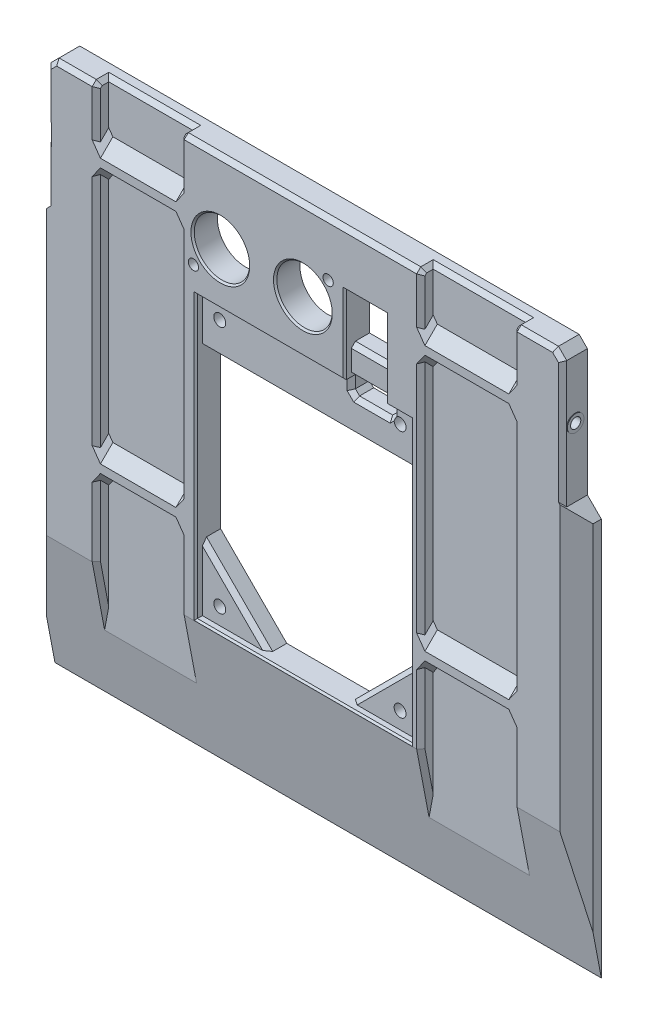
SolidWorks part; units mm, degrees
ref_plane "Front Plane" through (0, 0, 0) normal (0, 0, 1) x (1, 0, 0)
ref_plane "Top Plane" through (0, 0, 0) normal (0, 1, 0) x (1, 0, 0)
ref_plane "Right Plane" through (0, 0, 0) normal (1, 0, 0) x (0, 0, -1)
sketch "Sketch1" plane through (0, 0, 0) normal (0, 0, 1) x (1, 0, 0)
  line L1 (82.55, 82.55) -> (-82.55, 82.55)
  line L2 (82.55, 82.55) -> (82.55, -82.55)
  line L3 (82.55, -82.55) -> (-82.55, -82.55)
  line L4 (-82.55, 82.55) -> (-82.55, -82.55)
  line L5 (82.55, 82.55) -> (-82.55, -82.55) construction
  line L6 (82.55, -82.55) -> (-82.55, 82.55) construction
  point P0 (0, 0)
  dimension "D1" = 165.1
  dimension "D2" = 165.1
extrude "Boss-Extrude1" add sketch "Sketch1" along normal blind 7.5
sketch "Sketch2" plane through (0, 0, 7.5) normal (0, 0, 1) x (1, 0, 0)
  line L1 (-32.5, 42.5) -> (32.5, 42.5)
  line L2 (-32.5, 42.5) -> (-32.5, -42.5)
  line L3 (-32.5, -42.5) -> (32.5, -42.5)
  line L4 (32.5, 42.5) -> (32.5, -42.5)
  line L5 (-32.5, 42.5) -> (32.5, -42.5) construction
  line L6 (-32.5, -42.5) -> (32.5, 42.5) construction
  line L7 (12.5, 42.5) -> (25, 42.5)
  line L8 (12.5, 42.5) -> (12.5, 51.2227)
  line L9 (12.5, 51.2227) -> (25, 51.2227)
  line L10 (25, 42.5) -> (25, 51.2227)
  point P0 (0, 0)
  dimension "D1" = 65
  dimension "D2" = 85
  dimension "D3" = 12.5
  dimension "D4" = 7.5
extrude "Cut-Extrude1" cut sketch "Sketch2" against normal blind 2 contours L4 L1 L2 L3 | L1 L10 L9 L8
sketch "Sketch3" plane through (0, 0, 5.5) normal (0, 0, 1) x (1, 0, 0)
  line L1 (-27.25, -37.5) -> (27.25, -37.5) construction
  line L2 (-27.25, -37.5) -> (-27.25, 37.5) construction
  line L3 (-27.25, 37.5) -> (27.25, 37.5) construction
  line L4 (27.25, -37.5) -> (27.25, 37.5) construction
  line L5 (-27.25, -37.5) -> (27.25, 37.5) construction
  line L6 (-27.25, 37.5) -> (27.25, -37.5) construction
  circle A0 centre (-27.25, 37.5) radius 1.8
  circle A1 centre (27.25, 37.5) radius 1.8
  circle A3 centre (-27.25, -37.5) radius 1.8
  circle A4 centre (27.25, -37.5) radius 1.8
  point P0 (0, 0)
  point P7 (-27.25, 37.5)
  point P8 (27.25, 37.5)
  point P9 (-27.25, -37.5)
  point P10 (27.25, -37.5)
  dimension "D3" = 3.6
  dimension "D4" = 3.6
  dimension "D5" = 3.6
  dimension "D6" = 3.6
  dimension "D1" = 54.5
  dimension "D2" = 75
extrude "Cut-Extrude2" cut sketch "Sketch3" against normal through all
sketch "Sketch4" plane through (0, 0, 5.5) normal (0, 0, 1) x (1, 0, 0)
  line L0 (-32.5, 42.5) -> (-32.5, -42.5) construction
  line L1 (-32.5, 27.5) -> (32.5, 27.5)
  line L2 (-32.5, 27.5) -> (-32.5, -22.5)
  line L3 (-12.5, -42.5) -> (12.5, -42.5)
  line L4 (32.5, 27.5) -> (32.5, -22.5)
  line L5 (-32.5, -22.5) -> (-12.5, -42.5)
  line L6 (12.5, -42.5) -> (32.5, -22.5)
  line L7 (25, 42.5) -> (25, 51.2227) construction
  line L8 (12.5, 51.2227) -> (25, 51.2227)
  line L9 (12.5, 51.2227) -> (12.5, 66.2227)
  line L10 (12.5, 66.2227) -> (25, 66.2227)
  line L11 (25, 51.2227) -> (25, 66.2227)
  line L12 (25, 42.5) -> (25, 51.2227) construction
  line L13 (12.5, 42.5) -> (25, 42.5)
  line L14 (12.5, 42.5) -> (12.5, 37.5)
  line L15 (12.5, 37.5) -> (25, 37.5)
  line L16 (25, 42.5) -> (25, 37.5)
  point P1 (32.5, -42.5)
  point P2 (-32.5, -42.5)
  dimension "D1" = 70
  dimension "D2" = 15
  dimension "D3" = 5
extrude "Cut-Extrude5" cut sketch "Sketch4" against normal through all and the other way through all
sketch "Sketch5" plane through (0, 0, 0) normal (0, 0, -1) x (-1, 0, 0)
  line L0 (32.5, -42.5) -> (-32.5, -42.5) construction
  line L1 (32.5, 42.5) -> (-32.5, 42.5) construction
  line L2 (32.5, 42.5) -> (32.5, -42.5) construction
  line L3 (32.5, -42.5) -> (-32.5, -42.5) construction
  line L4 (-32.5, 42.5) -> (-32.5, -42.5) construction
  line L5 (-12.5, -42.5) -> (-32.5, -42.5) construction
  line L6 (-12.5, 42.5) -> (-12.5, 66.2227) construction
  line L7 (35.7, 66.3) -> (-7.5, 66.3) construction
  line L8 (35.7, 66.3) -> (35.7, 47.5) construction
  line L9 (35.7, 47.5) -> (-7.5, 47.5) construction
  line L10 (-7.5, 66.3) -> (-7.5, 47.5) construction
  line L11 (12.6047, 47.5) -> (12.6047, 58.15) construction
  line L12 (33.4547, 58.15) -> (-8.2453, 58.15) construction
  circle A0 centre (-7.5, 66.3) radius 1.55
  circle A1 centre (33.2, 50) radius 1.55
  circle A2 centre (0.1297, 58.15) radius 8.375
  circle A3 centre (25.0797, 58.15) radius 8.375
  dimension "D5" = 3.1
  dimension "D6" = 3.1
  dimension "D7" = 2.5
  dimension "D8" = 2.5
  dimension "D10" = 16.75
  dimension "D1" = 43.2
  dimension "D2" = 18.8
  dimension "D3" = 5
  dimension "D4" = 5
  dimension "D9" = 10.65
  dimension "D11" = 20.85
extrude "Cut-Extrude6" cut sketch "Sketch5" against normal through all contours A3 | A1 | A2 | A0
chamfer "Chamfer1" distance 0.5 angle 45 10 edges at (-16.7047, 58.15, 7.5) (-8.5047, 58.15, 7.5) (32.5, 0, 7.5) (-10, 42.5, 7.5) (25, 54.3614, 7.5) (18.75, 66.2227, 7.5) (12.5, 54.3614, 7.5) (0, -42.5, 7.5) (-32.5, 0, 7.5) (28.75, 42.5, 7.5)
chamfer "Chamfer2" distance 1.25 angle 45 2 edges at (12.5, 37.5, 2.75) (25, 37.5, 2.75)
chamfer "Chamfer3" distance 7.5 distance2 39.5 1 edges at (0, -82.55, 7.5)
sketch "Sketch12" plane through (0, 0, 7.5) normal (0, 0, 1) x (1, 0, 0)
  line L1 (-82.55, 82.55) -> (-77.55, 82.55)
  line L2 (-82.55, 82.55) -> (-82.55, 42.55)
  line L3 (-82.55, 42.55) -> (-77.55, 42.55)
  line L4 (-77.55, 82.55) -> (-77.55, 42.55)
  line L5 (82.55, 82.55) -> (78.35, 82.55)
  line L6 (82.55, 82.55) -> (82.55, 42.55)
  line L7 (82.55, 42.55) -> (78.35, 42.55)
  line L8 (78.35, 82.55) -> (78.35, 42.55)
  dimension "D1" = 40
  dimension "D2" = 5
  dimension "D3" = 4.2
extrude "Cut-Extrude11" cut sketch "Sketch12" against normal through all
sketch "Sketch13" plane through (-77.55, 0, 0) normal (-1, 0, 0) x (0, 0, 1)
  line L0 (3.75, 82.55) -> (3.75, 42.55) construction
  line L1 (0, 82.55) -> (7.5, 82.55) construction
  line L2 (0, 42.55) -> (7.5, 42.55) construction
  line L3 (3.75, 73.55) -> (3.75, 76.55) construction
  line L4 (3.75, 62.55) -> (0, 62.55) construction
  line L5 (0, 82.55) -> (0, 42.55) construction
  line L6 (3.75, 62.55) -> (3.75, 67.55) construction
  line L7 (3.75, 67.55) -> (3.75, 70.55) construction
  line L8 (3.75, 70.55) -> (3.75, 73.55) construction
  line L9 (3.75, 54.55) -> (3.75, 51.55) construction
  line L10 (3.75, 57.55) -> (3.75, 54.55) construction
  line L11 (3.75, 51.55) -> (3.75, 48.55) construction
  circle A0 centre (3.75, 67.55) radius 0.7
  circle A1 centre (3.75, 70.55) radius 0.7
  circle A2 centre (3.75, 73.55) radius 0.7
  circle A3 centre (3.75, 76.55) radius 0.7
  circle A4 centre (3.75, 48.55) radius 0.7
  circle A5 centre (3.75, 51.55) radius 0.7
  circle A6 centre (3.75, 54.55) radius 0.7
  circle A7 centre (3.75, 57.55) radius 0.7
  dimension "D5" = 1.4
  dimension "D6" = 1.4
  dimension "D7" = 1.4
  dimension "D8" = 1.4
  dimension "D1" = 3
  dimension "D2" = 5
  dimension "D3" = 3
  dimension "D4" = 3
extrude "Cut-Extrude12" cut sketch "Sketch13" against normal blind 10
sketch "Sketch14" plane through (-77.55, 0, 0) normal (-1, 0, 0) x (0, 0, 1)
  line L0 (3.75, 67.55) -> (3.75, 57.55) construction
  ellipse E0 centre (3.75, 62.55) end of major axis (-7.456, 62.55) minor radius 3.4258
extrude "Cut-Extrude13" cut sketch "Sketch14" against normal blind 1.5
sketch "Sketch15" plane through (78.35, 0, 0) normal (1, 0, 0) x (0, 0, -1)
  line L0 (-3.75, 82.55) -> (-3.75, 62.55) construction
  line L1 (0, 82.55) -> (-7.5, 82.55) construction
  circle A0 centre (-3.75, 62.55) radius 1.55
  dimension "D2" = 3.1
  dimension "D1" = 20
extrude "Cut-Extrude14" cut sketch "Sketch15" against normal blind 10
sketch "Sketch16" plane through (78.35, 0, 0) normal (1, 0, 0) x (0, 0, -1)
  circle A0 centre (-3.75, 62.55) radius 1.55
  circle A1 centre (-3.75, 62.55) radius 2.5
  dimension "D1" = 3.1
  dimension "D2" = 5
extrude "Boss-Extrude2" add sketch "Sketch16" along normal blind 0.2 contours A1 | A0
chamfer "Chamfer5" distance 5 angle 45 2 edges at (82.55, 42.55, 3.75) (-82.55, 42.55, 3.75)
chamfer "Chamfer6" distance 2.5 angle 45 2 edges at (78.35, 82.55, 3.75) (-77.55, 82.55, 3.75)
chamfer "Chamfer7" distance 1.25 angle 45 6 edges at (78.35, 60.9, 7.5) (77.1, 81.3, 7.5) (0.4, 82.55, 7.5) (-76.3, 81.3, 7.5) (-77.55, 72.9142, 7.5) (-77.55, 50.9358, 7.5)
chamfer "Chamfer8" distance 5 angle 45 2 edges at (82.55, -2.75, 7.5) (-82.55, -2.75, 7.5)
chamfer "Chamfer9" distance 1.25 angle 45 5 edges at (12.5, 40.625, 5.5) (13.125, 38.125, 5.5) (18.75, 37.5, 5.5) (24.375, 38.125, 5.5) (25, 40.625, 5.5)
chamfer "Chamfer10" distance 1.25 angle 45 2 edges at (18.75, 51.2227, 5.5) (18.75, 42.5, 5.5)
chamfer "Chamfer11" distance 1.25 angle 45 3 edges at (-22.5, -32.5, 5.5) (22.5, -32.5, 5.5) (0, 27.5, 5.5)
sketch "Sketch17" plane through (0, 82.55, 0) normal (0, 1, 0) x (1, 0, 0)
  line L0 (75.3322, -7.5) -> (-74.5322, -7.5) construction
  line L1 (-34.75, 0) -> (33, 0) construction
  line L2 (-34.75, 0) -> (-34.75, -7.5) construction
  line L3 (-34.75, -7.5) -> (33, -7.5) construction
  line L4 (33, 0) -> (33, -7.5) construction
  line L5 (-82.55, 0) -> (-65.05, 0)
  line L6 (-82.55, 0) -> (-82.55, -7.5)
  line L7 (-82.55, -7.5) -> (-65.05, -7.5)
  line L8 (-65.05, 0) -> (-65.05, -7.5)
  line L9 (-67.55, -3.05) -> (-67.55, -4.45) construction
  line L10 (68.35, -5.3) -> (68.35, -2.2) construction
  line L11 (82.55, 0) -> (65.85, 0)
  line L12 (82.55, 0) -> (82.55, -7.5)
  line L13 (82.55, -7.5) -> (65.85, -7.5)
  line L14 (65.85, 0) -> (65.85, -7.5)
  line L15 (75.85, 0) -> (-75.05, 0) construction
  line L16 (35.5, -7.5) -> (63.35, -7.5)
  line L17 (35.5, -7.5) -> (35.5, -3.75)
  line L18 (35.5, -3.75) -> (63.35, -3.75)
  line L19 (63.35, -7.5) -> (63.35, -3.75)
  line L20 (-62.55, -7.5) -> (-37.25, -7.5)
  line L21 (-62.55, -7.5) -> (-62.55, -3.75)
  line L22 (-62.55, -3.75) -> (-37.25, -3.75)
  line L23 (-37.25, -7.5) -> (-37.25, -3.75)
  dimension "D1" = 2.5
  dimension "D2" = 2.5
  dimension "D3" = 2.5
  dimension "D4" = 2.5
  dimension "D5" = 3.75
  dimension "D6" = 2.5
  dimension "D7" = 2.5
  dimension "D8" = 3.75
extrude "Cut-Extrude15" cut sketch "Sketch17" against normal through all contours L22 L23 L20 L21 | L18 L19 L16 L17
sketch "Sketch18" plane through (0, 0, 3.75) normal (0, 0, 1) x (1, 0, 0)
  line L0 (78.55, 62.55) -> (-76.05, 62.55) construction
  line L1 (78.55, 60.05) -> (78.55, 65.05) construction
  line L2 (-76.05, 59.3217) -> (-76.05, 65.7783) construction
  line L3 (-62.55, -62.8) -> (-62.55, 82.55) construction
  line L4 (-62.55, 62.55) -> (-37.25, 62.55)
  line L5 (-62.55, 62.55) -> (-62.55, 67.55)
  line L6 (-62.55, 67.55) -> (-37.25, 67.55)
  line L7 (-37.25, 62.55) -> (-37.25, 67.55)
  line L8 (-37.25, -62.8) -> (-37.25, 82.55) construction
  line L9 (-37.25, -43.05) -> (-37.25, 81.3) construction
  line L10 (-62.55, 62.55) -> (-37.25, 62.55)
  line L11 (-62.55, 62.55) -> (-62.55, 57.55)
  line L12 (-62.55, 57.55) -> (-37.25, 57.55)
  line L13 (-37.25, 62.55) -> (-37.25, 57.55)
  line L14 (63.35, -62.8) -> (63.35, 82.55) construction
  line L15 (63.35, 62.55) -> (35.5, 62.55)
  line L16 (63.35, 62.55) -> (63.35, 67.55)
  line L17 (63.35, 67.55) -> (35.5, 67.55)
  line L18 (35.5, 62.55) -> (35.5, 67.55)
  line L19 (35.5, -62.8) -> (35.5, 82.55) construction
  line L20 (63.35, -43.05) -> (63.35, 81.3) construction
  line L21 (35.5, 62.55) -> (63.35, 62.55)
  line L22 (35.5, 62.55) -> (35.5, 57.55)
  line L23 (35.5, 57.55) -> (63.35, 57.55)
  line L24 (63.35, 62.55) -> (63.35, 57.55)
  line L25 (-62.55, 22.55) -> (63.35, 22.55) construction
  line L26 (35.5, -12.45) -> (63.35, -12.45)
  line L27 (63.35, -17.45) -> (63.35, -12.45)
  line L28 (35.5, -17.45) -> (63.35, -17.45)
  line L29 (35.5, -17.45) -> (35.5, -12.45)
  line L30 (63.35, -22.45) -> (35.5, -22.45)
  line L31 (35.5, -17.45) -> (35.5, -22.45)
  line L32 (63.35, -17.45) -> (35.5, -17.45)
  line L33 (63.35, -17.45) -> (63.35, -22.45)
  line L34 (-62.55, -12.45) -> (-37.25, -12.45)
  line L35 (-37.25, -17.45) -> (-37.25, -12.45)
  line L36 (-62.55, -17.45) -> (-37.25, -17.45)
  line L37 (-62.55, -17.45) -> (-62.55, -12.45)
  line L38 (-62.55, -22.45) -> (-37.25, -22.45)
  line L39 (-37.25, -17.45) -> (-37.25, -22.45)
  line L40 (-62.55, -17.45) -> (-37.25, -17.45)
  line L41 (-62.55, -17.45) -> (-62.55, -22.45)
  line M1 (-37.25, -62.8) -> (-37.25, 82.55)
  line M3 (-62.55, 82.55) -> (-62.55, -62.8)
  dimension "D1" = 5
  dimension "D2" = 5
  dimension "D3" = 40
extrude "Boss-Extrude3" add sketch "Sketch18" along normal up to surface (3.75 mm away) contours L6 L4 M3 M1 | L12 L4 M3 M1 | L18 L15 L16 L17 | L24 L15 L22 L23 | L36 L34 M3 M1 | L38 L36 M3 M1 | L29 L28 L27 L26 | L33 L28 L31 L30 up to face at (-33.9547, 58.15, 7.5)
chamfer "Chamfer12" distance 3.75 angle 45 8 edges at (-49.9, -12.45, 7.5) (-49.9, -22.45, 7.5) (49.425, -22.45, 7.5) (49.425, -12.45, 7.5) (49.425, 57.55, 7.5) (49.425, 67.55, 7.5) (-49.9, 67.55, 7.5) (-49.9, 57.55, 7.5)
chamfer "Chamfer13" distance 1.25 angle 45 16 edges at (-37.25, -14.325, 5.625) (-62.55, 65.675, 5.625) (63.35, -14.325, 5.625) (63.35, 65.675, 5.625) (-37.25, 65.675, 5.625) (35.5, 65.675, 5.625) (35.5, 59.425, 5.625) (63.35, 59.425, 5.625) (63.35, -20.575, 5.625) (35.5, -14.325, 5.625) (35.5, -20.575, 5.625) (-62.55, -20.575, 5.625) (-37.25, -20.575, 5.625) (-62.55, -14.325, 5.625) (-62.55, 59.425, 5.625) (-37.25, 59.425, 5.625)
chamfer "Chamfer14" distance 1.25 angle 45 24 edges at (-62.55, -52.925, 5.625) (-62.55, -31.7589, 7.5) (-37.25, -52.925, 5.625) (-37.25, -31.7589, 7.5) (-62.55, 22.55, 7.5) (-37.25, 22.55, 7.5) (-62.55, 82.55, 5) (-62.55, 81.925, 6.875) (-62.55, 73.4339, 7.5) (-37.25, 73.4339, 7.5) (-37.25, 81.925, 6.875) (-37.25, 82.55, 5) (35.5, -52.925, 5.625) (35.5, -31.7589, 7.5) (35.5, 22.55, 7.5) (35.5, 82.55, 5) (35.5, 81.925, 6.875) (35.5, 73.4339, 7.5) (63.35, -52.925, 5.625) (63.35, -31.7589, 7.5) (63.35, 22.55, 7.5) (63.35, 82.55, 5) (63.35, 81.925, 6.875) (63.35, 73.4339, 7.5)
chamfer "Chamfer15" distance 1.25 angle 45 2 edges at (-49.9, 82.55, 3.75) (49.425, 82.55, 3.75)
